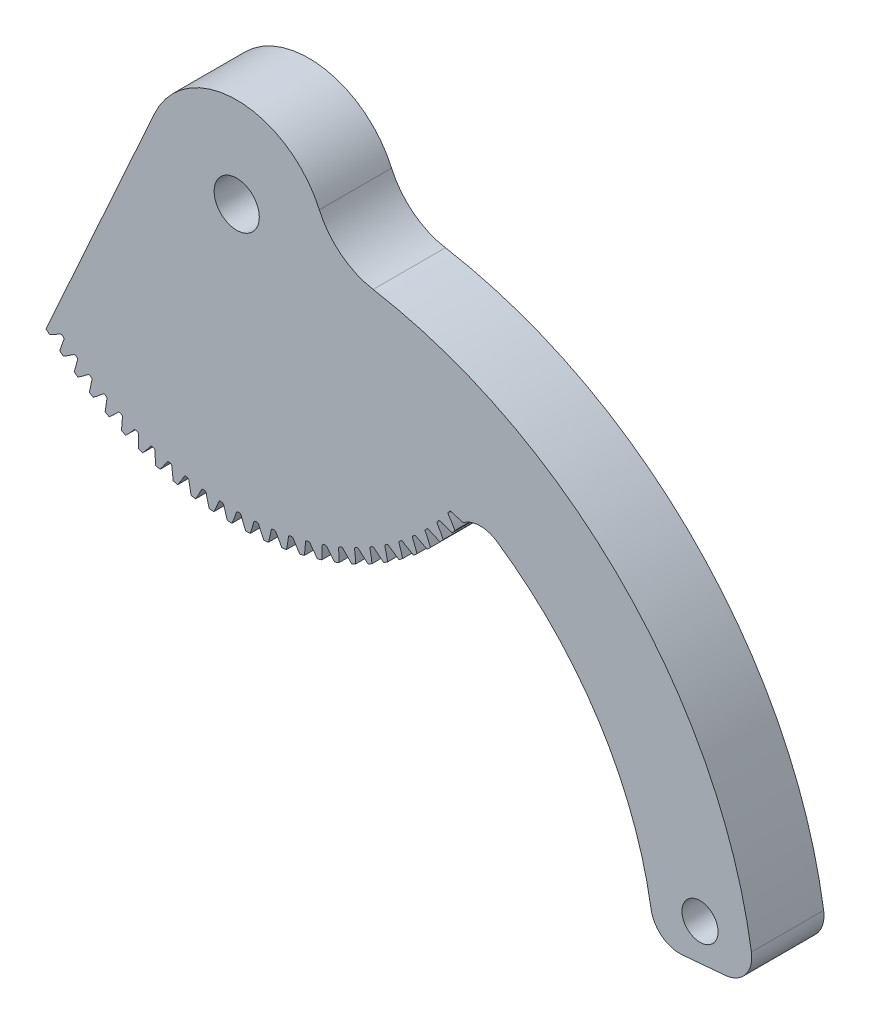
SolidWorks part; units mm, degrees
ref_plane "Front Plane" through (0, 0, 0) normal (0, 0, 1) x (1, 0, 0)
ref_plane "Top Plane" through (0, 0, 0) normal (0, 1, 0) x (1, 0, 0)
ref_plane "Right Plane" through (0, 0, 0) normal (1, 0, 0) x (0, 0, -1)
sketch "Sketch1" plane through (0, 0, 0) normal (0, 0, 1) x (1, 0, 0)
  line L0 (73.4184, -75.5444) -> (91.1307, -73.9948)
  line L2 (0, 0) -> (-33.521, -35.74) construction
  line L4 (10.16, -81.0788) -> (10.16, -17.5788) construction
  line L5 (110.9189, -72.2636) -> (10.16, -81.0788) construction
  line L6 (0, -55) -> (0, 55) construction
  line L7 (-33.521, -35.74) -> (-14.4729, 6.523)
  line L8 (0, 0) -> (41.5929, -25.9043) construction
  arc A0 (41.5929, -25.9043) -> (73.4184, -75.5444) centre (10.16, -81.0788) cw
  arc A1 (15.875, 0) -> (91.1307, -73.9948) centre (10.16, -81.0788) cw
  arc A2 (5.3552, -17.7609) -> (56.2442, -37.3924) centre (10.16, -81.0788) cw construction
  arc A3 (15.875, 0) -> (-14.4729, 6.523) centre (0, 0) ccw
  arc A4 (4.0099, -0.0318) -> (69.1477, -25.1603) centre (10.16, -81.0788) cw construction
  circle A5 centre (10.16, -81.0788) radius 72.39 construction
  arc A6 (-33.521, -35.74) -> (41.5929, -25.9043) centre (0, 0) ccw
  circle A10 centre (81.4431, -68.4681) radius 3.175
  point P14 (82.2745, -74.7696)
  dimension "D2" = 63.5
  dimension "D3" = 31.75
  dimension "D4" = 85
  dimension "D5" = 6.35
  dimension "D7" = 101.25
  dimension "D8" = 6.35
  dimension "D9" = 98
  dimension "D6" = 10.16
  dimension "D1" = 17.78
extrude "Extrude1" add sketch "Sketch1" along normal blind 12.7
sketch "Sketch2" plane through (0, 0, 12.7) normal (0, 0, 1) x (1, 0, 0)
  circle A0 centre (0, 0) radius 3.9688
  dimension "D1" = 7.9375
extrude "Extrude2" cut sketch "Sketch2" against normal through all
sketch "Sketch6" plane through (0, 0, 12.7) normal (0, 0, 1) x (1, 0, 0)
  circle A0 centre (0, 0) radius 49 construction
  arc A1 (-32.9289, -36.2862) -> (-31.1117, -37.8558) centre (0, 0) ccw
  spline S1 degree 3 poles (-2913.1902, 794.2298) (-20.1512, -69.1822) (-35.0469, -50.5114) (-31.0153, -37.5381) (-30.9775, -37.4192) (-30.9396, -37.3026) (-30.9015, -37.1882) (-30.8633, -37.0761) (-30.8251, -36.9663) (-30.7868, -36.8588) (-30.7485, -36.7535) (-30.7102, -36.6505) (-30.672, -36.5497) (-30.6339, -36.4511) (-30.5959, -36.3548) (-30.5577, -36.2608) (-30.5207, -36.1687) (-30.4764, -36.0713) (-30.4545, -35.9925) (-30.4271, -35.9445) (-30.4178, -35.9262) (-30.4089, -35.908) (-30.4005, -35.8896) (-30.3926, -35.8707) (-30.3851, -35.8513) (-30.3782, -35.8309) (-30.3718, -35.8092) (-30.3661, -35.7855) (-30.3614, -35.7592) (-30.3581, -35.7293) (-30.3573, -35.6946) (-30.3606, -35.6541) (-30.3707, -35.607) (-30.3909, -35.5545) (-30.4236, -35.5012) (-30.4814, -35.442) (-30.5597, -35.38) (-30.6324, -35.3116) (-30.6993, -35.263) (-30.7568, -35.2384) (-30.8117, -35.226) (-30.8598, -35.2229) (-30.9004, -35.2255) (-30.9346, -35.2314) (-30.9637, -35.2389) (-30.989, -35.2474) (-31.0116, -35.2565) (-31.0322, -35.266) (-31.0514, -35.2758) (-31.0695, -35.286) (-31.087, -35.2966) (-31.104, -35.3076) (-31.1207, -35.3191) (-31.1374, -35.331) (-31.181, -35.365) (-31.2557, -35.3981) (-31.3456, -35.4562) (-31.4314, -35.5062) (-31.5189, -35.5576) (-31.6086, -35.6092) (-31.7006, -35.6613) (-31.7947, -35.7137) (-31.8911, -35.7666) (-31.9897, -35.8198) (-32.0905, -35.8733) (-32.1936, -35.9271) (-32.2989, -35.9812) (-32.4065, -36.0355) (-32.5164, -36.09) (-32.6286, -36.1446) (-44.8775, -42.02) (-65.516, -29.9981) (1209.4186, -2766.6665) knots -7.352363 -7.352363 -7.352363 -7.352363 0.047527 0.070709 0.093503 0.11591 0.137929 0.15956 0.180803 0.201659 0.222127 0.242207 0.2619 0.281205 0.300122 0.318652 0.336793 0.354547 0.377312 0.3811 0.384833 0.388531 0.392222 0.395938 0.399723 0.403632 0.407739 0.412139 0.416964 0.422383 0.428619 0.435944 0.444641 0.454908 0.466665 0.478633 0.5 0.521367 0.533335 0.545092 0.555359 0.564056 0.571381 0.577617 0.583036 0.587861 0.592261 0.596368 0.600277 0.604062 0.607778 0.611469 0.615167 0.6189 0.622688 0.645453 0.663207 0.681348 0.699878 0.718795 0.7381 0.757793 0.777873 0.798341 0.819197 0.84044 0.862071 0.88409 0.906497 0.929291 0.952473 8.352317 8.352317 8.352317 8.352317 only from (-31.1117, -37.8558) to (-32.9289, -36.2862) construction
  spline S2 degree 3 poles (-31.1117, -37.8558) (-31.0922, -37.79) (-31.0605, -37.6837) (-31.0153, -37.5381) (-30.9775, -37.4192) (-30.9396, -37.3026) (-30.9015, -37.1882) (-30.8633, -37.0761) (-30.8251, -36.9663) (-30.7868, -36.8588) (-30.7485, -36.7535) (-30.7102, -36.6505) (-30.672, -36.5497) (-30.6339, -36.4511) (-30.5959, -36.3548) (-30.5577, -36.2608) (-30.5207, -36.1687) (-30.4764, -36.0713) (-30.4545, -35.9925) (-30.4271, -35.9445) (-30.4178, -35.9262) (-30.4089, -35.908) (-30.4005, -35.8896) (-30.3926, -35.8707) (-30.3851, -35.8513) (-30.3782, -35.8309) (-30.3718, -35.8092) (-30.3661, -35.7855) (-30.3614, -35.7592) (-30.3581, -35.7293) (-30.3573, -35.6946) (-30.3606, -35.6541) (-30.3707, -35.607) (-30.3909, -35.5545) (-30.4236, -35.5012) (-30.4814, -35.442) (-30.5597, -35.38) (-30.6324, -35.3116) (-30.6993, -35.263) (-30.7568, -35.2384) (-30.8117, -35.226) (-30.8598, -35.2229) (-30.9004, -35.2255) (-30.9346, -35.2314) (-30.9637, -35.2389) (-30.989, -35.2474) (-31.0116, -35.2565) (-31.0322, -35.266) (-31.0514, -35.2758) (-31.0695, -35.286) (-31.087, -35.2966) (-31.104, -35.3076) (-31.1207, -35.3191) (-31.1374, -35.331) (-31.181, -35.365) (-31.2557, -35.3981) (-31.3456, -35.4562) (-31.4314, -35.5062) (-31.5189, -35.5576) (-31.6086, -35.6092) (-31.7006, -35.6613) (-31.7947, -35.7137) (-31.8911, -35.7666) (-31.9897, -35.8198) (-32.0905, -35.8733) (-32.1936, -35.9271) (-32.2989, -35.9812) (-32.4065, -36.0355) (-32.5164, -36.09) (-32.6286, -36.1446) (-32.7661, -36.2106) (-32.8666, -36.2573) (-32.9289, -36.2862) knots 0.009918 0.009918 0.009918 0.009918 0.047527 0.070709 0.093503 0.11591 0.137929 0.15956 0.180803 0.201659 0.222127 0.242207 0.2619 0.281205 0.300122 0.318652 0.336793 0.354547 0.377312 0.3811 0.384833 0.388531 0.392222 0.395938 0.399723 0.403632 0.407739 0.412139 0.416964 0.422383 0.428619 0.435944 0.444641 0.454908 0.466665 0.478633 0.5 0.521367 0.533335 0.545092 0.555359 0.564056 0.571381 0.577617 0.583036 0.587861 0.592261 0.596368 0.600277 0.604062 0.607778 0.611469 0.615167 0.6189 0.622688 0.645453 0.663207 0.681348 0.699878 0.718795 0.7381 0.757793 0.777873 0.798341 0.819197 0.84044 0.862071 0.88409 0.906497 0.929291 0.952473 0.990082 0.990082 0.990082 0.990082
extrude "Cut-Extrude1" cut sketch "Sketch6" against normal through all
pattern_circular "CirPattern1" count 26 every 3.75 about axis through (0, 0, 12.7) along (0, 0, 1) of "Cut-Extrude1"
fillet "Fillet1" radius 12.7 1 edges at (15.875, 0, 6.35)
fillet "Fillet2" radius 5.08 3 edges at (91.1307, -73.9948, 6.35) (73.4184, -75.5444, 6.35) (41.5929, -25.9043, 6.35)
ref_axis "Axis1" through (0, 0, 0) along (0, 0, 1)
